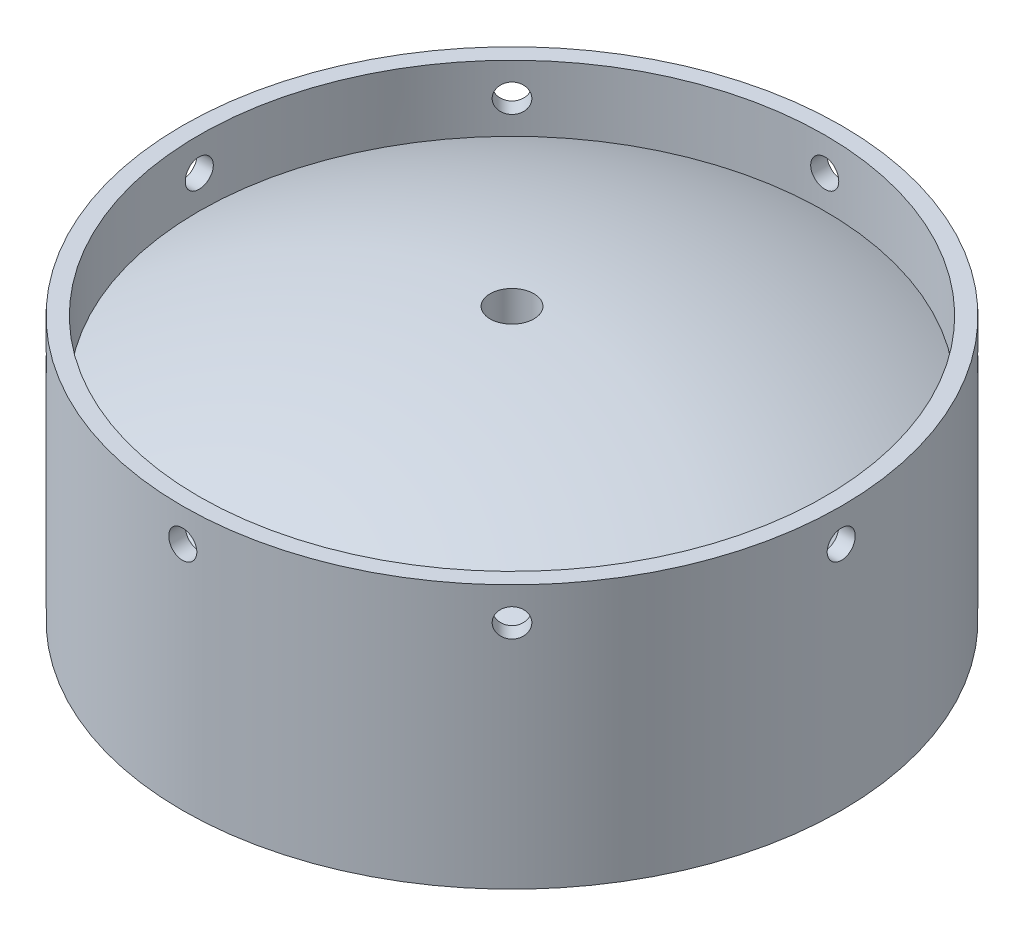
SolidWorks part; units mm, degrees
material "6061-T6 (SS)"
ref_plane "Front Plane" through (0, 0, 0) normal (0, 0, 1) x (1, 0, 0)
ref_plane "Top Plane" through (0, 0, 0) normal (0, 1, 0) x (1, 0, 0)
ref_plane "Right Plane" through (0, 0, 0) normal (1, 0, 0) x (0, 0, -1)
ref_axis "Axis1" through (0, 127.061, 0) along (0, -1, 0)
sketch "Sketch1" plane through (0, 0, 0) normal (0, 0, 1) x (1, 0, 0)
  line L0 (-63.5, 0) -> (-63.5, 50.8)
  line L1 (-60.325, 0) -> (-63.5, 0)
  line L2 (0, 127.061) -> (0, -81.9141) construction
  line L3 (55, 0) -> (-55, 0) construction
  line L7 (-60.325, 50.8) -> (-63.5, 50.8)
  line L8 (-63.5, 0) -> (-60.325, 0)
  line L10 (-4.2164, 52.3822) -> (-4.2164, 45.3936)
  line L11 (-60.325, 38.1) -> (-60.325, 50.8)
  line L16 (-60.325, 0) -> (-56.8743, 19.5701)
  arc A0 (-56.8743, 19.5701) -> (-44.4991, 37.4124) centre (-37.8243, 19.5701) cw
  arc A1 (-44.4991, 37.4124) -> (-4.2164, 45.3936) centre (0, -81.5364) cw
  arc A3 (-60.325, 38.1) -> (-4.2164, 52.3822) centre (0, -81.5364) cw
  point P0 (-56.892, 19.5635)
  dimension "D5" = 19.05
  dimension "D6" = 127
  dimension "D7" = 133.985
  dimension "D8" = 50.8
  dimension "D2" = 260
  dimension "D9" = 12.7
  dimension "D10" = 3.175
  dimension "D13" = 4.2164
  dimension "D15" = 3.175
  dimension "D16" = 63.5
revolve "Revolve2" add sketch "Sketch1" angle 360 about axis through (0, 127.061, 0) along (0, -1, 0) region at (-62.7089, 25.4, 0)
sketch "Sketch2" plane through (0, 0, 0) normal (0, 0, 1) x (1, 0, 0)
  line L0 (0, 127.061) -> (0, -81.9141) construction
  line L1 (0, 87.1374) -> (-97.8719, 87.1374)
  line L2 (0, 87.1374) -> (0, -26.2798)
  line L3 (0, -26.2798) -> (-97.8719, -26.2798)
  line L4 (-97.8719, 87.1374) -> (-97.8719, -26.2798)
revolve "Cut-Revolve1" [suppressed] cut sketch "Sketch2" angle 315 about axis through (0, 127.061, 0) along (0, -1, 0)
ref_plane "Plane1" through (0, 44.45, 0) normal (0, 1, 0) x (1, 0, 0)
ref_axis "Axis2" through (0, 44.45, -88.99) along (0, 0, 1)
hole_wizard "#3 (0.213) Diameter Hole1" positions "3DSketch3" profile "Sketch5" hole size "#3" standard "ANSI Inch" end condition up to next
sketch3d "3DSketch3"
  line L0 (0, 44.45, -88.99) -> (0, 44.45, 88.99) construction
  point P0 (0, 44.45, 63.5)
sketch "Sketch5" plane through (0, 44.45, 63.5) normal (1, 0, 0) x (0, -1, 0)
  line L0 (0, 0) -> (0, 3.175)
  line L1 (0, 3.175) -> (2.7051, 3.175)
  line L2 (2.7051, 3.175) -> (2.7051, 0)
  line L5 (2.7051, 0) -> (0, 0)
  line L11 (0, -6.35) -> (0, 107.95) construction
  dimension "Thru Hole Dia." = 5.4102
  dimension "Thru Hole Depth" = 3.175
pattern_circular "CirPattern1" count 8 over 360 about axis through (0, 127.061, 0) along (0, -1, 0) of "#3 (0.213) Diameter Hole1"
cosmetic thread "Cosmetic Thread1" parameters "D2"=6.35
ref_plane "Plane2" through (0, 0, 0) normal (0, -1, 0) x (-1, 0, 0)
sketch "Sketch7" plane through (0, 0, 0) normal (0, -1, 0) x (-1, 0, 0)
  circle A0 centre (0, 0) radius 56.515
  dimension "D1" = 113.03
extrude "Boss-Extrude2" [suppressed] add sketch "Sketch7" against normal blind 41.91 separate body
combine bodies "Combine2" [suppressed] operation type subtract main body 113 bodies to subtract 110
sketch "Sketch8" plane through (0, 0, 0) normal (0, 0, 1) x (1, 0, 0)
  line L0 (0, 127.061) -> (0, -81.9141) construction
  line L1 (0, 89.8009) -> (92.4947, 89.8009)
  line L2 (0, 89.8009) -> (0, -18.1338)
  line L3 (0, -18.1338) -> (92.4947, -18.1338)
  line L4 (92.4947, 89.8009) -> (92.4947, -18.1338)
revolve "Cut-Revolve2" [suppressed] cut sketch "Sketch8" angle 300 about axis through (0, 127.061, 0) along (0, -1, 0) other way angle 30 reverse direction yes
